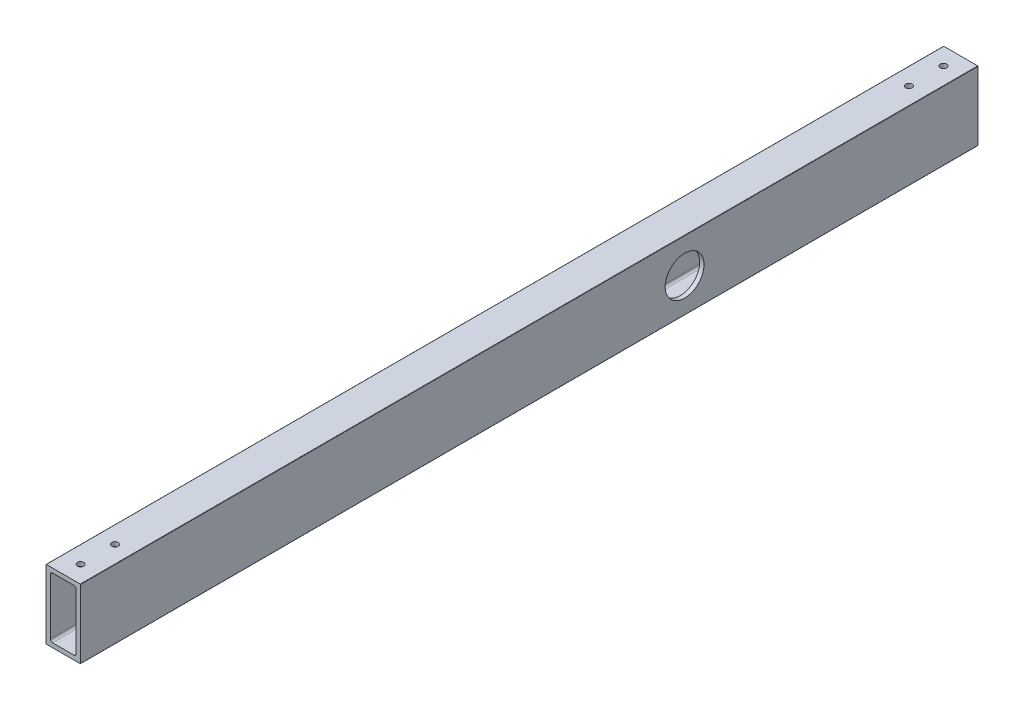
SolidWorks part; units mm, degrees
material "1060 Alloy"
ref_plane "Front Plane" through (0, 0, 0) normal (0, 0, 1) x (1, 0, 0)
ref_plane "Top Plane" through (0, 0, 0) normal (0, 1, 0) x (1, 0, 0)
ref_plane "Right Plane" through (0, 0, 0) normal (1, 0, 0) x (0, 0, -1)
ref_plane "Plane1" through (0, 0, 0) normal (0, 0, -1) x (-1, 0, 0)
sketch "Sketch1" plane through (0, 0, 0) normal (0, 0, -1) x (-1, 0, 0)
  line L0 (-3.175, 46.0375) -> (-3.175, 4.7625)
  line L1 (-4.7625, 3.175) -> (-20.6375, 3.175)
  line L2 (-22.225, 4.7625) -> (-22.225, 46.0375)
  line L3 (-20.6375, 47.625) -> (-4.7625, 47.625)
  line L4 (0, 0.254) -> (0, 50.546)
  line L5 (-0.254, 50.8) -> (-25.146, 50.8)
  line L6 (-25.4, 50.546) -> (-25.4, 0.254)
  line L7 (-25.146, 0) -> (-0.254, 0)
  arc A0 (-3.175, 4.7625) -> (-4.7625, 3.175) centre (-4.7625, 4.7625) cw
  arc A1 (-20.6375, 3.175) -> (-22.225, 4.7625) centre (-20.6375, 4.7625) cw
  arc A2 (-22.225, 46.0375) -> (-20.6375, 47.625) centre (-20.6375, 46.0375) cw
  arc A3 (-4.7625, 47.625) -> (-3.175, 46.0375) centre (-4.7625, 46.0375) cw
  arc A4 (-0.254, 0) -> (0, 0.254) centre (-0.254, 0.254) ccw
  arc A5 (0, 50.546) -> (-0.254, 50.8) centre (-0.254, 50.546) ccw
  arc A6 (-25.146, 50.8) -> (-25.4, 50.546) centre (-25.146, 50.546) ccw
  arc A7 (-25.4, 0.254) -> (-25.146, 0) centre (-25.146, 0.254) ccw
extrude "Boss-Extrude1" add sketch "Sketch1" against normal blind 660.4
sketch "Sketch2" plane through (0, 50.8, 0) normal (0, 1, 0) x (1, 0, 0)
  line L0 (0.254, -660.4) -> (25.146, -660.4) construction
  line L1 (25.146, -330.2) -> (0, -330.2) construction
  line L2 (25.146, -660.4) -> (25.146, 0) construction
  line L3 (0, -660.4) -> (0, 0) construction
  circle A0 centre (12.7, -647.7) radius 2.3813
  circle A1 centre (12.7, -622.3) radius 2.3813
  circle A2 centre (12.7, -38.1) radius 2.3812
  circle A3 centre (12.7, -12.7) radius 2.3813
  dimension "D1" = 4.7625
  dimension "D2" = 4.7625
  dimension "D3" = 12.7
  dimension "D4" = 25.4
extrude "Cut-Extrude1" cut sketch "Sketch2" against normal through all
sketch "Sketch5" plane through (25.4, 0, 0) normal (1, 0, 0) x (0, 0, -1)
  line L0 (-660.4, 50.546) -> (0, 50.546) construction
  line L2 (0, 50.546) -> (0, 0.254) construction
  circle A0 centre (-215.9, 25.146) radius 14.2875
  dimension "D1" = 28.575
  dimension "D2" = 25.4
  dimension "D3" = 215.9
extrude "Cut-Extrude2" cut sketch "Sketch5" against normal through all
